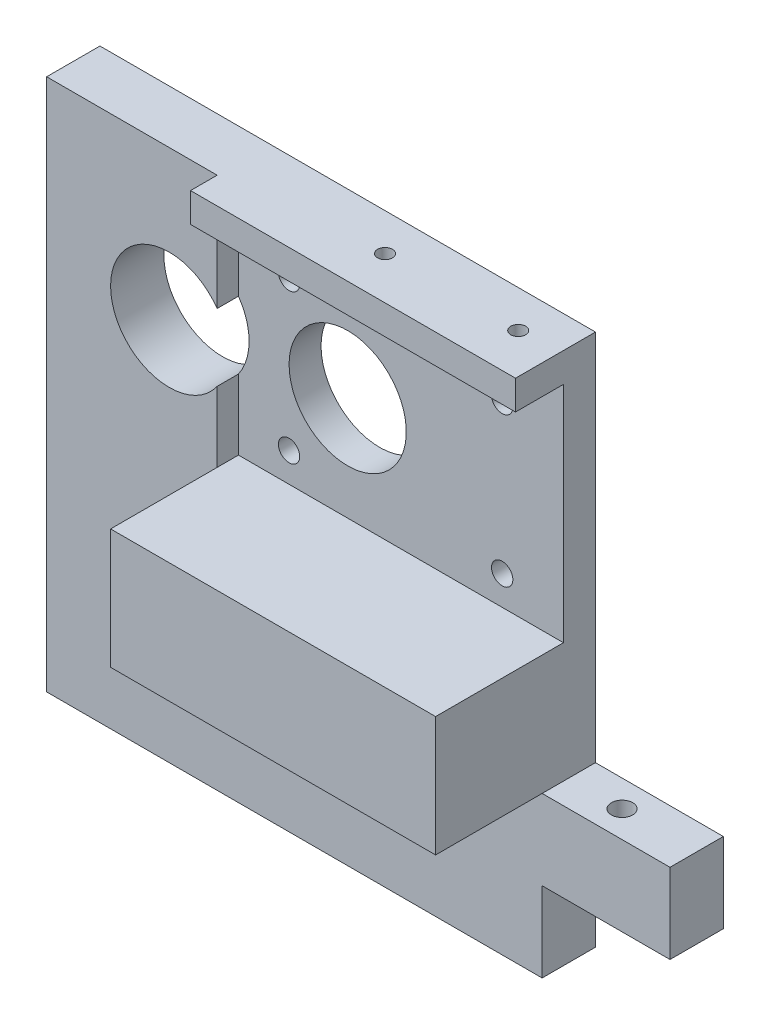
SolidWorks part; units mm, degrees
ref_plane "Front Plane" through (0, 0, 0) normal (0, 0, 1) x (1, 0, 0)
ref_plane "Top Plane" through (0, 0, 0) normal (0, 1, 0) x (1, 0, 0)
ref_plane "Right Plane" through (0, 0, 0) normal (1, 0, 0) x (0, 0, -1)
sketch "Sketch1" plane through (0, 0, 0) normal (0, 0, 1) x (1, 0, 0)
  line L1 (-76.1871, 64.9281) -> (16.8129, 64.9281)
  line L2 (-76.1871, 64.9281) -> (-76.1871, -35.0719)
  line L3 (-76.1871, -35.0719) -> (16.8129, -35.0719)
  line L4 (16.8129, 64.9281) -> (16.8129, -35.0719)
  dimension "D1" = 93
  dimension "D2" = 100
extrude "Boss-Extrude2" add sketch "Sketch1" along normal blind 10 contours L1 L4 L3 L2
sketch "Sketch3" plane through (0, 0, 0) normal (0, 0, -1) x (-1, 0, 0)
  line L0 (76.1871, -35.0719) -> (-16.8129, -35.0719) construction
  line L1 (-16.8129, 64.9281) -> (-6.8129, 64.9281)
  line L2 (-16.8129, 64.9281) -> (-16.8129, -35.0719)
  line L3 (-16.8129, -35.0719) -> (-6.8129, -35.0719)
  line L4 (-6.8129, 64.9281) -> (-6.8129, -35.0719)
  line L5 (-16.8129, 64.9281) -> (-16.8129, -35.0719) construction
  dimension "D1" = 0
  dimension "D2" = 0
  dimension "D3" = 10
  dimension "D4" = 100
extrude "Boss-Extrude3" add sketch "Sketch3" along normal blind 0.01
sketch "Sketch4" plane through (16.8129, 0, 0) normal (1, 0, 0) x (0, 0, -1)
  line L0 (-10, 64.9281) -> (-10, -35.0719) construction
  line L1 (-10, -5.0719) -> (0.01, -5.0719)
  line L2 (-10, -5.0719) -> (-10, -20.0719)
  line L3 (-10, -20.0719) -> (0.01, -20.0719)
  line L4 (0.01, -5.0719) -> (0.01, -20.0719)
  line L5 (0.01, 64.9281) -> (0.01, -35.0719) construction
  line L6 (-10, -35.0719) -> (0.01, -35.0719) construction
  dimension "D1" = 15
  dimension "D2" = 15
extrude "Boss-Extrude4" add sketch "Sketch4" along normal blind 24
sketch "Sketch5" plane through (0, -5.0719, 0) normal (0, 1, 0) x (1, 0, 0)
  line L0 (40.8129, -10) -> (16.8129, -10) construction
  line L2 (16.8129, 0.01) -> (16.8129, -10) construction
  circle A0 centre (26.8129, -5) radius 2
  dimension "D2" = 4
  dimension "D3" = 10
  dimension "D1" = 5
extrude "Cut-Extrude1" cut sketch "Sketch5" against normal blind 50
sketch "Sketch6" plane through (0, 0, -0.01) normal (0, 0, -1) x (-1, 0, 0)
  line L0 (-16.8129, -35.0719) -> (-6.8129, -35.0719) construction
  line L1 (-16.8129, -20.0719) -> (-16.8129, -35.0719) construction
  circle A0 centre (-1.8129, -24.5719) radius 7.5
  dimension "D1" = 15
  dimension "D2" = 10.5
  dimension "D3" = 15
sketch "Sketch7" plane through (0, 0, 0) normal (0, 0, -1) x (-1, 0, 0)
  line L0 (76.1871, -35.0719) -> (-6.8129, -35.0719) construction
  line L2 (-16.8129, 64.9281) -> (-16.8129, -5.0719) construction
  circle A0 centre (23.6871, 36.9281) radius 11
  dimension "D1" = 22
  dimension "D2" = 72
  dimension "D3" = 40.5
extrude "Cut-Extrude3" cut sketch "Sketch7" against normal blind 50
extrude "Extrude-Thin1" add sketch "Sketch7<2>" along normal blind 1 from surface thin starting at face at (-12.6871, 36.9281, 10) thin type one direction reverse wall 2
sketch "Sketch7<2>" plane through (0, 0, 0) normal (0, 0, -1) x (-1, 0, 0) same geometry as "Sketch7"
extrude "Extrude-Thin2" add sketch "Sketch6" along normal blind 1 from surface thin starting at face at (-0.4371, 1.1781, 10) thin type one direction reverse wall 2
sketch "Sketch8" plane through (0, 64.9281, 0) normal (0, 1, 0) x (1, 0, 0)
  line L0 (-76.1871, -10) -> (16.8129, -10) construction
  line L1 (16.8129, 0.01) -> (6.8129, 0.01)
  line L2 (16.8129, 0.01) -> (16.8129, -10)
  line L3 (16.8129, -10) -> (6.8129, -10)
  line L4 (6.8129, 0.01) -> (6.8129, -10)
  line L5 (16.8129, 0.01) -> (6.8129, -10) construction
  line L6 (16.8129, -10) -> (6.8129, 0.01) construction
  line L7 (6.8129, 0.01) -> (6.8129, 0) construction
  circle A0 centre (9.3129, -6.99) radius 1.4
  circle A1 centre (-15.6871, -6.99) radius 1.4
  point P4 (11.8129, -4.995)
  dimension "D1" = 25
  dimension "D3" = 2.8
  dimension "D5" = 7
  dimension "D6" = 7
extrude "Cut-Extrude4" cut sketch "Sketch8" against normal blind 5.5 contours A1 | A0 region at (-15.6871, 64.9281, 6.99)
sketch "Sketch14" plane through (0, 0, 10) normal (0, 0, 1) x (1, 0, 0)
  line L0 (16.8129, 64.9281) -> (16.8129, -5.0719) construction
  line L1 (-44.1871, 17.4281) -> (16.8129, 17.4281)
  line L2 (-44.1871, 17.4281) -> (-44.1871, 59.4281)
  line L3 (-44.1871, 59.4281) -> (16.8129, 59.4281)
  line L4 (16.8129, 17.4281) -> (16.8129, 59.4281)
  circle A0 centre (-23.6871, 36.9281) radius 9 construction
  dimension "D1" = 42
  dimension "D2" = 19.5
  dimension "D3" = 20.5
extrude "Cut-Extrude8" cut sketch "Sketch14" against normal blind 4
sketch "Sketch15" plane through (0, 0, 0) normal (0, 0, -1) x (-1, 0, 0)
  circle A0 centre (23.6871, 36.9281) radius 10
  circle A1 centre (23.6871, 36.9281) radius 11 construction
  dimension "D1" = 20
  dimension "D2" = 0
sketch "Sketch16" plane through (0, 0, 10) normal (0, 0, 1) x (1, 0, 0)
  line L1 (-44.1871, 59.4281) -> (16.8129, 59.4281)
  line L2 (-44.1871, 59.4281) -> (-44.1871, 64.9281)
  line L3 (-44.1871, 64.9281) -> (16.8129, 64.9281)
  line L4 (16.8129, 59.4281) -> (16.8129, 64.9281)
extrude "Boss-Extrude5" add sketch "Sketch16" along normal blind 5
sketch "Sketch17" plane through (0, 0, 10) normal (0, 0, 1) x (1, 0, 0)
  line L0 (16.8129, 17.4281) -> (16.8129, -5.0719) construction
  line L1 (-44.1871, 17.4281) -> (16.8129, 17.4281)
  line L2 (-44.1871, 17.4281) -> (-44.1871, -5.0719)
  line L3 (-44.1871, -5.0719) -> (16.8129, -5.0719)
  line L4 (16.8129, 17.4281) -> (16.8129, -5.0719)
extrude "Boss-Extrude6" add sketch "Sketch17" along normal blind 20
sketch "Sketch19" plane through (0, 0, 0) normal (0, 0, -1) x (-1, 0, 0)
  line L0 (-16.8129, 64.9281) -> (-16.8129, -5.0719) construction
  circle A0 centre (53.1871, 36.9281) radius 11
  circle A1 centre (23.6871, 36.9281) radius 10 construction
  dimension "D1" = 22
  dimension "D3" = 0
  dimension "D2" = 70
extrude "Cut-Extrude11" cut sketch "Sketch19" against normal blind 15
sketch "Sketch20" plane through (0, 0, 6) normal (0, 0, 1) x (1, 0, 0)
  circle A0 centre (-34.6871, 50.9281) radius 2
  circle A1 centre (5.3129, 50.9281) radius 2
  circle A2 centre (-34.6871, 22.9281) radius 2
  circle A3 centre (5.3129, 22.9281) radius 2
  circle A4 centre (-23.6871, 36.9281) radius 11 construction
  dimension "D1" = 4
  dimension "D2" = 4
  dimension "D3" = 4
  dimension "D4" = 4
  dimension "D5" = 28
  dimension "D6" = 28
  dimension "D7" = 0
  dimension "D8" = 40
  dimension "D9" = 11
  dimension "D10" = 14
extrude "Cut-Extrude12" cut sketch "Sketch20" against normal blind 10
